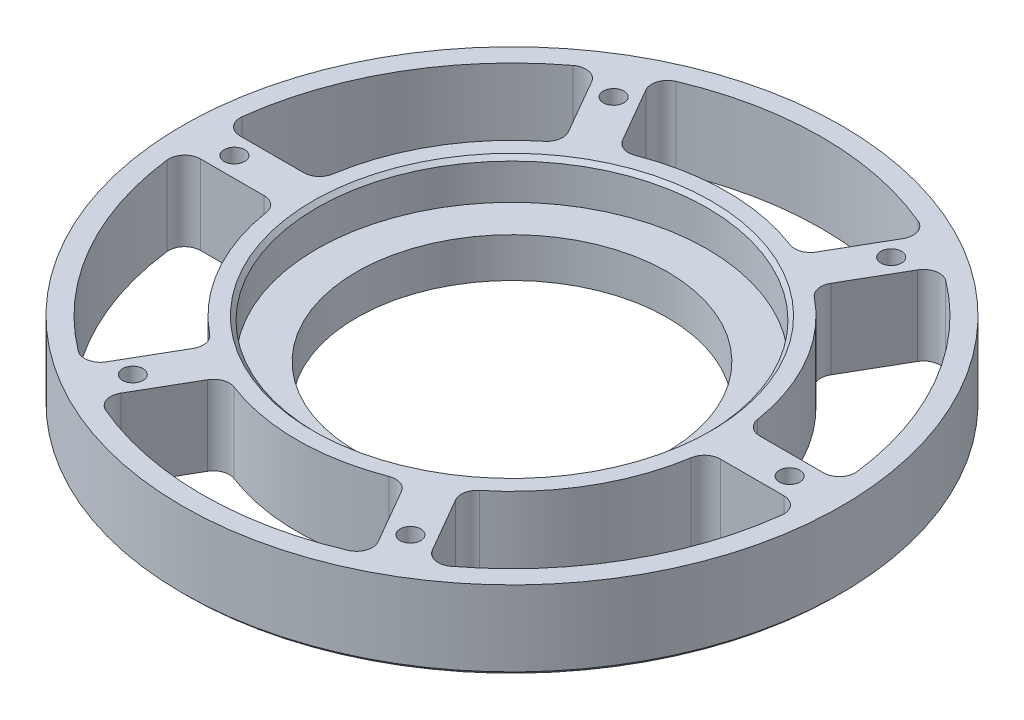
SolidWorks part; units mm, degrees
ref_plane "Front Plane" through (0, 0, 0) normal (0, 0, 1) x (1, 0, 0)
ref_plane "Top Plane" through (0, 0, 0) normal (0, 1, 0) x (1, 0, 0)
ref_plane "Right Plane" through (0, 0, 0) normal (1, 0, 0) x (0, 0, -1)
sketch "Sketch2" plane through (0, 0, 0) normal (1, 0, 0) x (0, 0, -1)
  line L0 (-39.2125, 0) -> (-83.0999, 0)
  line L1 (-83.0999, 0) -> (-83.0999, 20)
  line L2 (-83.0999, 20) -> (-49.2125, 20)
  line L3 (-49.2125, 20) -> (-49.2125, 10)
  line L4 (-49.2125, 10) -> (-39.2125, 10)
  line L5 (-39.2125, 10) -> (-39.2125, 0)
  dimension "D1" = 83.0999
  dimension "D2" = 20
  dimension "D3" = 10
  dimension "D4" = 49.2125
  dimension "D5" = 10
ref_axis "Axis1" through (0, -1, 0) along (0, 1, 0)
revolve "Revolve1" add sketch "Sketch2" angle 360 about axis through (0, -1, 0) along (0, 1, 0)
hole_wizard "#6 (0.204) Diameter Hole1" positions "Sketch6" profile "Sketch7" hole size "#6" standard "ANSI Inch" end condition through all
sketch "Sketch6" plane through (0, 20, 0) normal (0, 1, 0) x (1, 0, 0)
  line L0 (0, 0) -> (-69.8201, 120.932) construction
  line L2 (0, 0) -> (0, 109.0908) construction
  point P0 (-35, 60.6218)
  dimension "D1" = 30
  dimension "D2" = 70
sketch "Sketch7" plane through (-35, 20, -60.6218) normal (1, 0, 0) x (0, 0, 1)
  line L0 (0, 0) -> (0, 20)
  line L1 (0, 20) -> (2.5908, 20)
  line L2 (2.5908, 20) -> (2.5908, 0)
  line L5 (2.5908, 0) -> (0, 0)
  line L11 (0, -6.35) -> (0, 107.95) construction
  dimension "Thru Hole Dia." = 5.1816
  dimension "Thru Hole Depth" = 20
pattern_circular "CirPattern3" count 6 over 360 about axis through (0, -1, 0) along (0, 1, 0) of "#6 (0.204) Diameter Hole1"
sketch "Sketch8" plane through (0, 20, 0) normal (0, 1, 0) x (1, 0, 0)
  line L0 (-34.6397, 69.9978) -> (-22.6606, 49.2493)
  line L1 (34.6397, 69.9978) -> (22.6606, 49.2493)
  line L2 (0, 0) -> (-35, 60.6218) construction
  line L4 (0, 0) -> (0, 93.9995) construction
  arc A0 (-22.6606, 49.2493) -> (22.6606, 49.2493) centre (0, 0) cw
  arc A1 (-34.6397, 69.9978) -> (34.6397, 69.9978) centre (0, 0) cw
  circle A2 centre (0, 0) radius 49.2125 construction
  circle A3 centre (0, 0) radius 83.0999 construction
  dimension "D1" = 5
  dimension "D2" = 5
  dimension "D3" = 5
extrude "Cut-Extrude1" cut sketch "Sketch8" against normal through all
fillet "Fillet1" radius 4 4 edges at (34.6397, 10, -69.9978) (22.6606, 10, -49.2493) (-34.6397, 10, -69.9978) (-22.6606, 10, -49.2493)
pattern_circular "CirPattern4" count 6 over 360 about axis through (0, -1, 0) along (0, 1, 0) of "Cut-Extrude1", "Fillet1"
chamfer "Chamfer1" distance 1 angle 45 1 edges at (0, 20, -49.2125)
chamfer "Chamfer2" distance 1 angle 45 1 edges at (0, 0, -83.0999)
equation "\"TubeDiameter\" = 6.5433in"
equation "\"D1@Sketch2\"=\"TubeDiameter\"/2"
